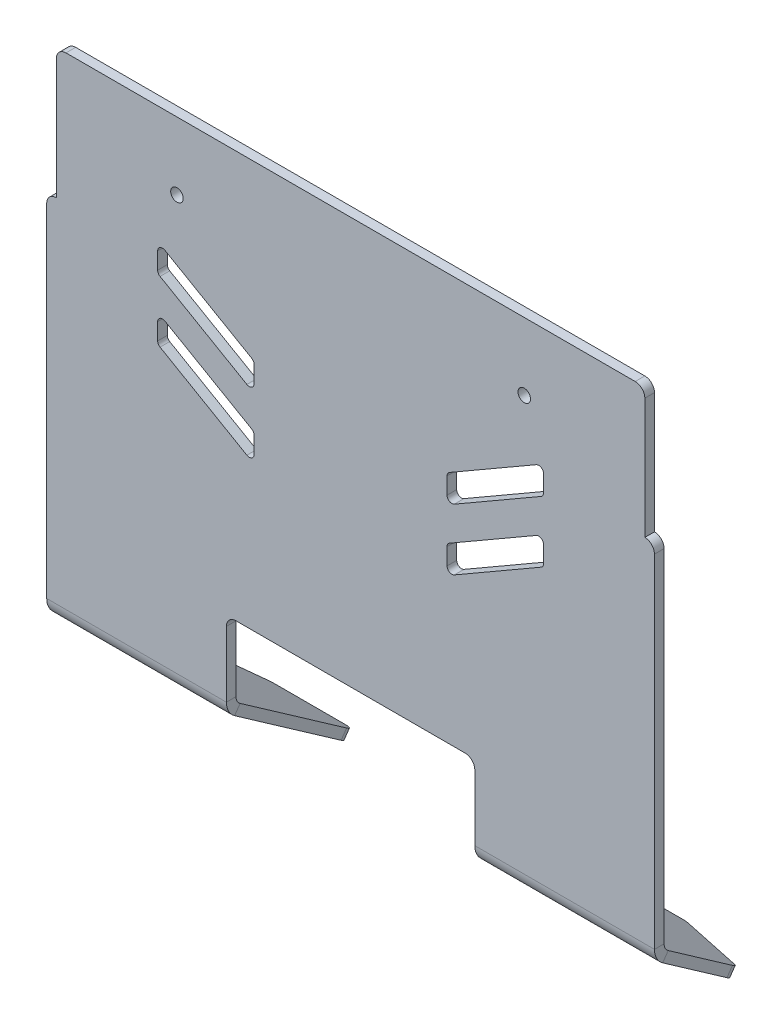
SolidWorks part; units mm, degrees
note: The reader was unsure of these and kept them because the rebuilt part matched: bend radius of "BaseBend1".
material "2024 Alloy (SN)"
ref_plane "Front Plane" through (0, 0, 0) normal (0, 0, 1) x (1, 0, 0)
ref_plane "Top Plane" through (0, 0, 0) normal (0, 1, 0) x (1, 0, 0)
ref_plane "Right Plane" through (0, 0, 0) normal (1, 0, 0) x (0, 0, -1)
sketch "Sketch1" plane through (0, 0, 0) normal (1, 0, 0) x (0, 0, -1)
  line L2 (0, 0) -> (0, -101)
  line L6 (0, -101) -> (24.5746, -118.2073)
  dimension "D1" = 30
  dimension "D2" = 125
  dimension "D3" = 101
sheet metal parameters "Sheet-Metal1" thickness 2 parameters "D1"=2
sheet metal parameters "Sheet-Metal2" thickness 1.5 parameters "D1"=2.5
base flange "Base-Flange1" sketch "Sketch1" end condition mid plane depth 126 reverse direction no thickness 2 reverse thickness direction no bend radius 2
bend "BaseBend1" bend radius 2 bend angle 55 parameters "D5"=10
sketch "Sketch2" plane through (0, 0, 2) normal (0, 0, 1) x (1, 0, 0)
  line L0 (63, -119.8456) -> (-63, -119.8456) construction
  line L1 (-25.75, -84.3456) -> (25.75, -84.3456)
  line L2 (-25.75, -84.3456) -> (-25.75, -119.8456)
  line L3 (-25.75, -119.8456) -> (25.75, -119.8456)
  line L4 (25.75, -84.3456) -> (25.75, -119.8456)
  line L5 (-25.75, -84.3456) -> (25.75, -119.8456) construction
  line L6 (-25.75, -119.8456) -> (25.75, -84.3456) construction
  point P0 (0, -102.0956)
  dimension "D1" = 51.5
  dimension "D2" = 35.5
extrude "Cut-Extrude1" cut sketch "Sketch2" against normal through all both and the other way through all
fillet "Fillet1" radius 2 2 edges at (25.75, -84.3456, 1) (-25.75, -84.3456, 1)
chamfer "Chamfer1" distance 20 angle 30 2 edges at (63, -119.0264, -24.001) (-63, -119.0264, -24.001)
sketch "Sketch3" plane through (0, 0, 2) normal (0, 0, 1) x (1, 0, 0)
  line L0 (-36, -14) -> (36, -14) construction
  line L1 (0, 0) -> (0, -14) construction
  line L2 (63, 0) -> (-63, 0) construction
  circle A0 centre (-36, -14) radius 1.3
  circle A1 centre (36, -14) radius 1.3
  dimension "D3" = 2.6
  dimension "D1" = 14
  dimension "D2" = 72
extrude "Cut-Extrude2" cut sketch "Sketch3" against normal blind 2
sketch "Sketch4" plane through (0, 0, 2) normal (0, 0, 1) x (1, 0, 0)
  line L1 (-63, 0) -> (-61, 0)
  line L2 (-63, 0) -> (-63, -27)
  line L3 (-63, -27) -> (-61, -27)
  line L4 (-61, 0) -> (-61, -27)
  line L5 (63, 0) -> (61, 0)
  line L6 (63, 0) -> (63, -27)
  line L7 (63, -27) -> (61, -27)
  line L8 (61, 0) -> (61, -27)
  dimension "D1" = 2
  dimension "D2" = 27
extrude "Cut-Extrude3" cut sketch "Sketch4" against normal blind 2
fillet "Fillet2" radius 2 10 edges at (63, -112.4034, -14.5422) (43, -119.0264, -24.001) (25.75, -119.0264, -24.001) (-63, -112.4034, -14.5422) (-43, -119.0264, -24.001) (-25.75, -119.0264, -24.001) (-63, -27, 1) (63, -27, 1) (61, 0, 1) (-61, 0, 1)
sketch "Sketch5" plane through (0, 0, 2) normal (0, 0, 1) x (1, 0, 0)
  line L5 (0, -84.3456) -> (0, 0) construction
  line L6 (-23.75, -84.3456) -> (23.75, -84.3456) construction
  line L9 (59, 0) -> (-59, 0) construction
  line L38 (-40, -24.3234) -> (-40, -30.0969)
  line L39 (-40, -30.0969) -> (-20, -41.6439)
  line L40 (-20, -41.6439) -> (-20, -35.8704)
  line L41 (-20, -35.8704) -> (-40, -24.3234)
  line L42 (-40, -37.0251) -> (-20, -48.5721)
  line L43 (-20, -48.5721) -> (-20, -54.3456)
  line L44 (-20, -54.3456) -> (-40, -42.7986)
  line L45 (-40, -42.7986) -> (-40, -37.0251)
  line L57 (40, -42.7986) -> (40, -37.0251)
  line L58 (20, -54.3456) -> (40, -42.7986)
  line L59 (20, -48.5721) -> (20, -54.3456)
  line L60 (40, -37.0251) -> (20, -48.5721)
  line L61 (20, -35.8704) -> (40, -24.3234)
  line L62 (20, -41.6439) -> (20, -35.8704)
  line L63 (40, -30.0969) -> (20, -41.6439)
  line L64 (40, -24.3234) -> (40, -30.0969)
  dimension "D9" = 60
  dimension "D10" = 20
  dimension "D11" = 20
  dimension "D12" = 30
  dimension "D13" = 6
  dimension "D14" = 5
extrude "Cut-Extrude4" cut sketch "Sketch5" against normal blind 10
fillet "Fillet3" radius 1 16 edges at (40, -30.0969, 1) (40, -42.7986, 1) (-20, -41.6439, 1) (-20, -54.3456, 1) (-40, -42.7986, 1) (-40, -30.0969, 1) (20, -41.6439, 1) (20, -54.3456, 1) (40, -37.0251, 1) (40, -24.3234, 1) (-20, -35.8704, 1) (-20, -48.5721, 1) (20, -48.5721, 1) (20, -35.8704, 1) (-40, -37.0251, 1) (-40, -24.3234, 1)
flat pattern "Flat-Pattern1" [suppressed]
sketch "Bend-Lines1" plane through (0, 0, 0) normal (0, 0, -1) x (-1, 0, 0)
  line L0 (63, -101.3988) -> (-63, -101.3988) construction
  line L2 (63, -101.3988) -> (25.75, -101.3988) construction
  line L3 (-25.75, -101.3988) -> (-63, -101.3988) construction
  point P20 (59.5525, 0)
  point P21 (59.5525, -10)
sketch3d "Bounding-Box1" [suppressed]
  line L0 (126, 0, 0) -> (126, -131.7975, 0) construction
  line L1 (0, 0, 0) -> (0, -131.7975, 0) construction
  line L2 (126, 0, 0) -> (0, 0, 0) construction
  line L3 (126, -131.7975, 0) -> (0, -131.7975, 0) construction
bend of the flat pattern "Flatten-<BaseBend1>1"
flat pattern "Flat-Pattern2" [suppressed]
sketch "Bend-Lines2" plane through (0, 0, 0) normal (0, 1, 0) x (1, 0, 0)
sketch "Bounding-Box2" [suppressed] plane through (0, 0, 0) normal (0, 1, 0) x (1, 0, 0)
